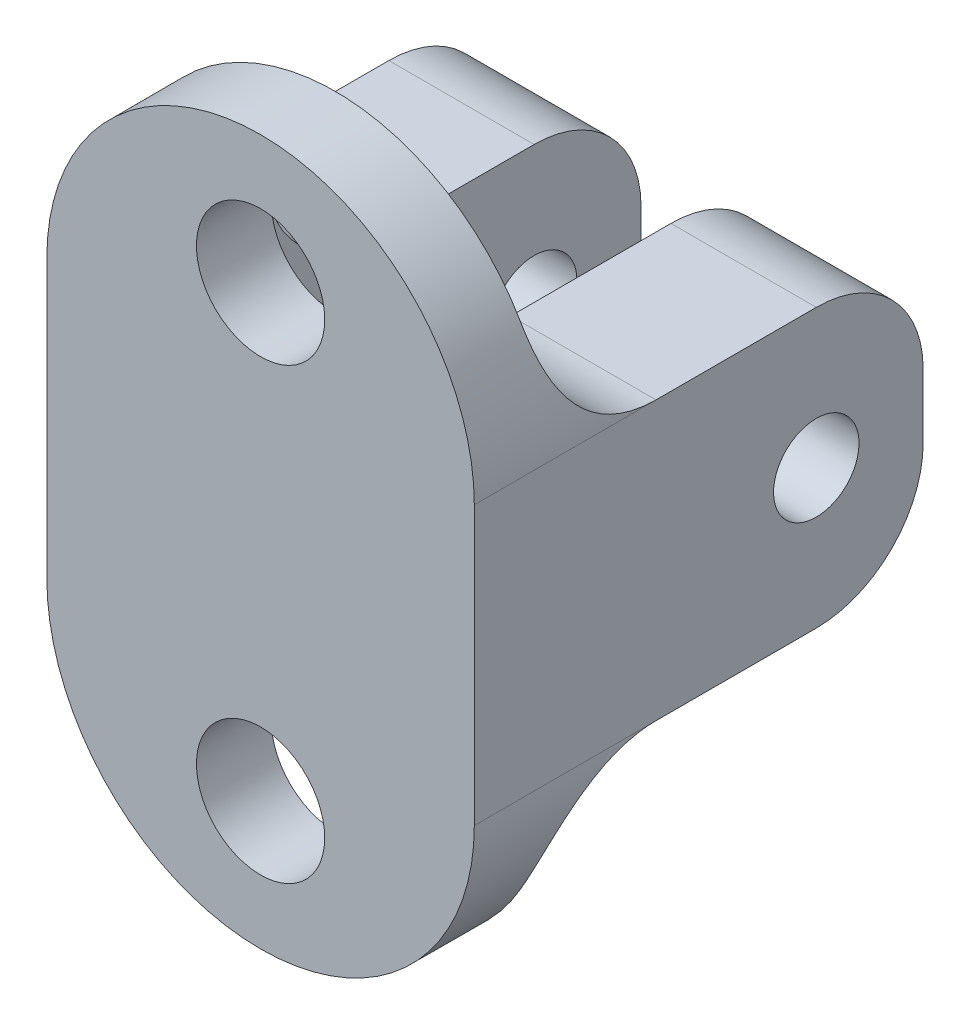
SolidWorks part; units mm, degrees
ref_plane "Plan de face" through (0, 0, 0) normal (0, 0, 1) x (1, 0, 0)
ref_plane "Plan de dessus" through (0, 0, 0) normal (0, 1, 0) x (1, 0, 0)
ref_plane "Plan de droite" through (0, 0, 0) normal (1, 0, 0) x (0, 0, -1)
sketch "Esquisse1" plane through (0, 0, 0) normal (0, 0, 1) x (1, 0, 0)
  line L2 (-8.2445, 16.7633) -> (-8.2445, 3.7633)
  line L4 (11.7555, 16.7633) -> (11.7555, 3.7633)
  arc A1 (-8.2445, 16.7633) -> (11.7555, 16.7633) centre (1.7555, 16.7633) cw
  arc A2 (-8.2445, 3.7633) -> (11.7555, 3.7633) centre (1.7555, 3.7633) ccw
  circle A3 centre (1.7555, 20.7633) radius 3
  circle A4 centre (1.7555, -0.2367) radius 3
  point P12 (1.7555, 26.7633)
  point P13 (1.7555, -6.2367)
  dimension "D5" = 6
  dimension "D1" = 20
  dimension "D2" = 13
  dimension "D6" = 6
extrude "Boss.-Extru.1" add sketch "Esquisse1" along normal blind 5
sketch "Esquisse2" plane through (11.7555, 0, 0) normal (1, 0, 0) x (0, 0, -1)
  line L0 (0, 3.7633) -> (0, 16.7633) construction
  line L1 (0, 16.7633) -> (12.5, 16.7633)
  line L2 (0, 16.7633) -> (0, 3.7633)
  line L3 (0, 3.7633) -> (12.5, 3.7633)
  line L4 (17.5, 11.7633) -> (17.5, 8.7633)
  circle A0 centre (12.5, 10.2633) radius 2
  arc A1 (12.5, 3.7633) -> (17.5, 8.7633) centre (12.5, 8.7633) ccw
  arc A2 (12.5, 16.7633) -> (17.5, 11.7633) centre (12.5, 11.7633) cw
  dimension "D1" = 12.5
  dimension "D2" = 5
  dimension "D3" = 17.5
extrude "Boss.-Extru.2" add sketch "Esquisse2" against normal blind 20
sketch "Esquisse3" plane through (0, 3.7633, 0) normal (0, -1, 0) x (-1, 0, 0)
  line L1 (1.4445, 0) -> (-4.9555, 0)
  line L2 (1.4445, 0) -> (1.4445, 20)
  line L3 (1.4445, 20) -> (-4.9555, 20)
  line L4 (-4.9555, 0) -> (-4.9555, 20)
  line L5 (-11.7555, -5) -> (-11.7555, 10) construction
  dimension "D1" = 20
  dimension "D2" = 6.4
  dimension "D3" = 6.8
extrude "Enlèv. mat.-Extru.1" cut sketch "Esquisse3" against normal blind 20
fillet "Congé1" radius 5 4 edges at (-4.8445, 16.7633, 0) (8.3555, 16.7633, 0) (-4.8445, 3.7633, 0) (8.3555, 3.7633, 0)
sketch "Esquisse4" plane through (0, 0, 5) normal (0, 0, 1) x (1, 0, 0)
  line L1 (-14.1554, 31.2431) -> (19.6966, 31.2431)
  line L2 (-14.1554, 31.2431) -> (-14.1554, -12.1906)
  line L3 (-14.1554, -12.1906) -> (19.6966, -12.1906)
  line L4 (19.6966, 31.2431) -> (19.6966, -12.1906)
extrude "Enlèv. mat.-Extru.2" cut sketch "Esquisse4" against normal blind 1.5
